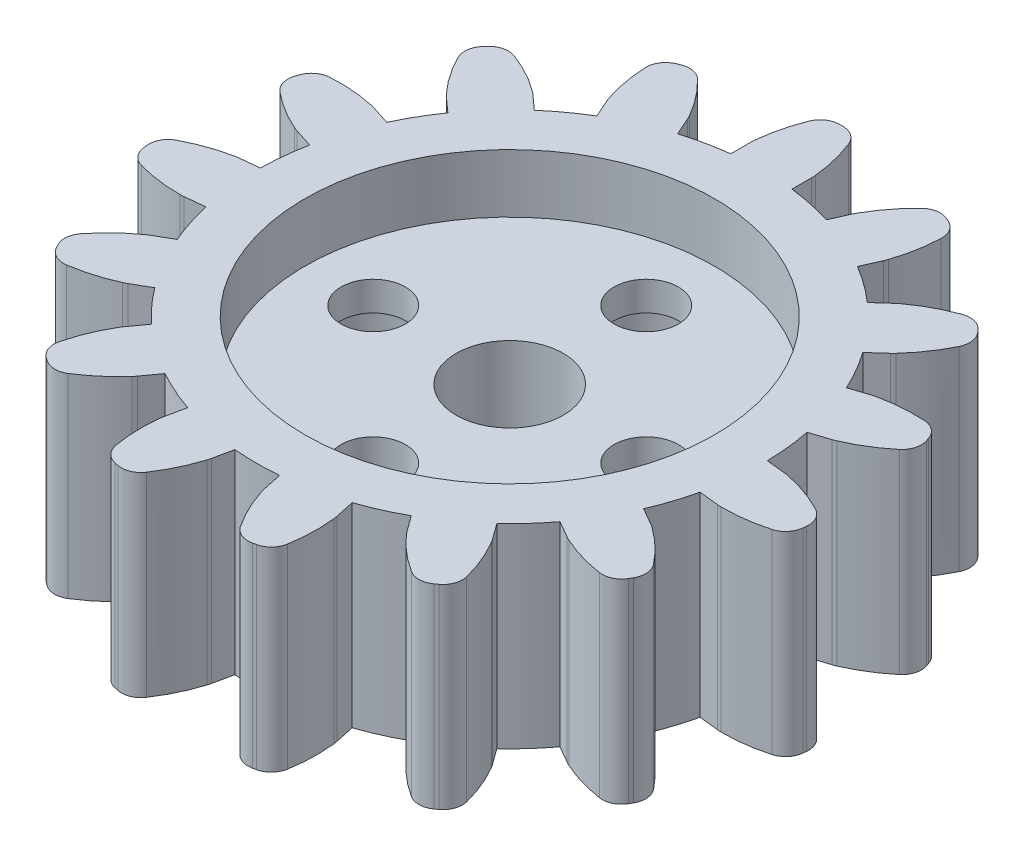
SolidWorks part; units mm, degrees
ref_plane "Plan de face" through (0, 0, 0) normal (0, 0, 1) x (1, 0, 0)
ref_plane "Plan de dessus" through (0, 0, 0) normal (0, 1, 0) x (1, 0, 0)
ref_plane "Plan de droite" through (0, 0, 0) normal (1, 0, 0) x (0, 0, -1)
sketch "Esquisse1" plane through (0, 0, 0) normal (0, 1, 0) x (1, 0, 0)
  line L0 (0, 0) -> (3.5345, 16.6285) construction
  line L1 (0, 0) -> (-3.5345, 16.6285) construction
  line L2 (0, 0) -> (0, 17) construction
  line L3 (-1.57, 12.9048) -> (1.57, 12.9048) construction
  line L5 (-0.74, 16.9839) -> (0, 0) construction
  line L6 (0, 0) -> (-2.7029, 12.7159)
  line L7 (-1.57, 12.9048) -> (1.57, 12.9048) construction
  line L8 (-1.57, 12.9048) -> (-1.57, 14.0073)
  line L9 (-1.57, 14.0073) -> (1.57, 14.0073) construction
  line L10 (1.57, 12.9048) -> (1.57, 14.0073)
  line L11 (-1.44, 14.9307) -> (0, 0) construction
  line L12 (0, 0) -> (2.7029, 12.7159)
  line L13 (-0.74, 16.9839) -> (0.74, 16.9839) construction
  line L14 (-1.44, 14.9307) -> (1.44, 14.9307) construction
  circle A0 centre (0, 0) radius 13 construction
  circle A1 centre (0, 0) radius 17 construction
  circle A2 centre (0, 0) radius 15 construction
  circle A3 centre (0, 0) radius 14.095 construction
  arc A4 (-1.57, 12.9048) -> (-2.7029, 12.7159) centre (0, 0) ccw
  arc A5 (1.57, 12.9048) -> (2.7029, 12.7159) centre (0, 0) cw
  arc A6 (-0.74, 16.9839) -> (0.74, 16.9839) centre (0, 0) cw
  spline S0 degree 2 poles (-0.74, 16.9839) (-1.4393, 15.5634) (-1.57, 14.0073) knots 0 0 0 1 1 1
  spline S1 degree 2 poles (0.74, 16.9839) (1.4393, 15.5634) (1.57, 14.0073) knots 0 0 0 1 1 1
  dimension "D1" = 26
  dimension "D2" = 28.19
  dimension "D3" = 30
  dimension "D4" = 34
  dimension "D5" = 24
  dimension "D6" = 12
  dimension "D7" = 3.14
  dimension "D8" = 2.88
  dimension "D9" = 1.48
extrude "Boss.-Extru.2" add sketch "Esquisse1" along normal blind 10 contours S1 A6 S0 L8 A4 L6 L12 A5 L10 region at (0, 0, -10.0419)
fillet "Congé1" radius 1 2 edges at (0.74, 5, -16.9839) (-0.74, 5, -16.9839)
fillet "Congé2" radius 2 2 edges at (1.57, 5, -14.0073) (-1.57, 5, -14.0073)
pattern_circular "Répétition circulaire1" count 15 over 360 about axis through (0, 10, 0) along (0, -1, 0) of "Boss.-Extru.2", "Congé1", "Congé2"
sketch "Esquisse2" plane through (0, 10, 0) normal (0, 1, 0) x (1, 0, 0)
  circle A0 centre (0, 0) radius 10.5
  dimension "D1" = 21
extrude "Enlèv. mat.-Extru.1" cut sketch "Esquisse2" against normal blind 3
sketch "Esquisse3" plane through (0, 7, 0) normal (0, 1, 0) x (1, 0, 0)
  line L0 (0, 7) -> (0, 0) construction
  circle A0 centre (0, 0) radius 2.75
  circle A1 centre (0, 7) radius 1.65
  circle A5 centre (7, 0) radius 1.65
  circle A6 centre (0, -7) radius 1.65
  circle A7 centre (-7, 0) radius 1.65
  point P14 (0, 0)
  dimension "D1" = 5.5
  dimension "D2" = 3.3
  dimension "D3" = 7
  dimension "D4" = 4
extrude "Enlèv. mat.-Extru.2" cut sketch "Esquisse3" against normal through all
sketch "Esquisse4" plane through (0, 0, 0) normal (0, -1, 0) x (1, 0, 0)
  circle A0 centre (0, 7) radius 2.75
  circle A4 centre (7, 0) radius 2.75
  circle A5 centre (0, -7) radius 2.75
  circle A6 centre (-7, 0) radius 2.75
  point P10 (0, 7)
  point P13 (0, 0)
  dimension "D1" = 5.5
  dimension "D2" = 4
extrude "Enlèv. mat.-Extru.3" cut sketch "Esquisse4" against normal offset from surface (5.5 mm away) 1.5 up to face at (0, 7, 2.75)
